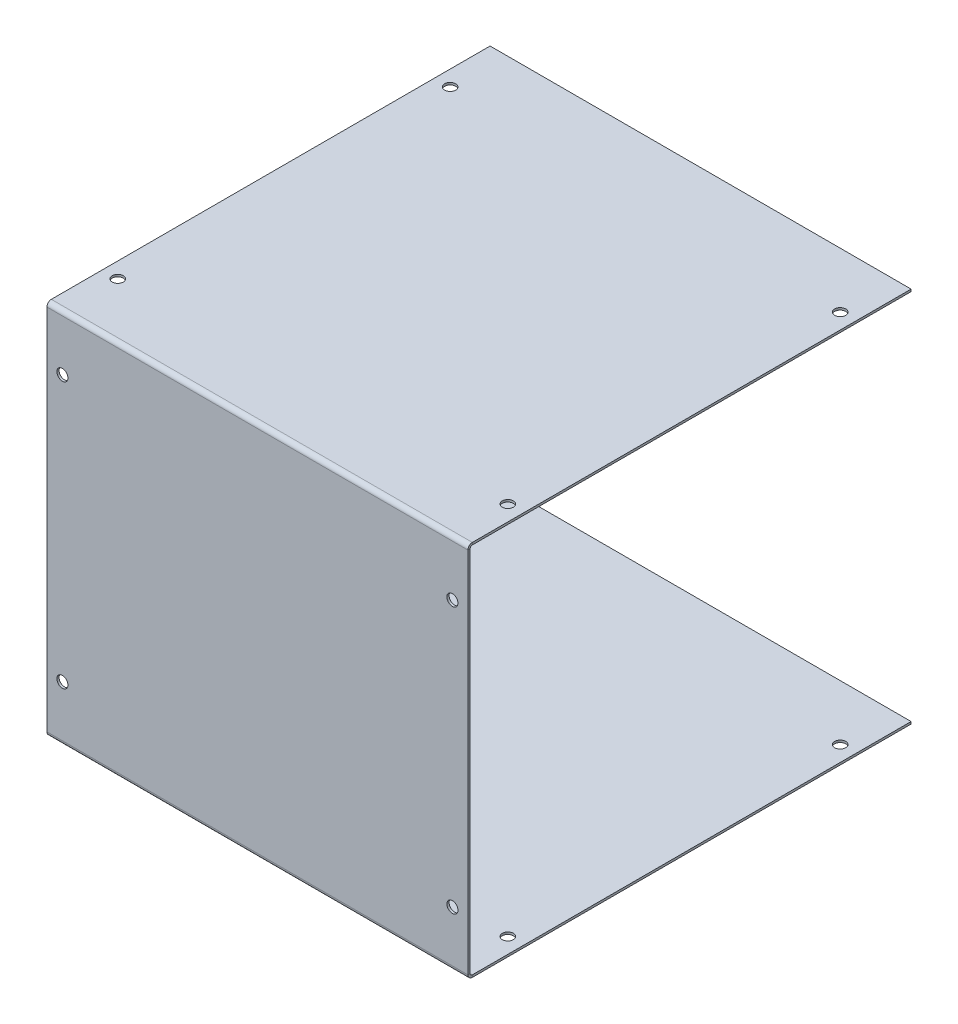
SolidWorks part; units mm, degrees
note: The reader was unsure of these and kept them because the rebuilt part matched: thickness of "Base-Flange1", "Edge-Flange5", "Sheet-Metal1", "Sheet-Metal4", "Sheet-Metal6", "Sheet-Metal7"; flange length of "Edge-Flange5".
material "St.37"
ref_plane "Front Plane" through (0, 0, 0) normal (0, 0, 1) x (1, 0, 0)
ref_plane "Top Plane" through (0, 0, 0) normal (0, 1, 0) x (1, 0, 0)
ref_plane "Right Plane" through (0, 0, 0) normal (1, 0, 0) x (0, 0, -1)
sketch "Sketch1" plane through (0, 0, 0) normal (0, 0, 1) x (1, 0, 0)
  line L1 (-95, -85) -> (95, -85)
  line L2 (-95, -85) -> (-95, 85)
  line L3 (-95, 85) -> (95, 85)
  line L4 (95, -85) -> (95, 85)
  line L5 (-95, -85) -> (95, 85) construction
  line L6 (-95, 85) -> (95, -85) construction
  point P0 (0, 0)
  dimension "D1" = 170
  dimension "D2" = 190
base flange "Base-Flange1" sketch "Sketch1" thickness 1 reverse thickness direction no parameters "D1"=1
sketch "Sketch23" plane through (0, 0, 0) normal (0, 0, 1) x (1, 0, 0)
  line L1 (-95, 85) -> (-95, -85) construction
  line L2 (-95, -85) -> (95, -85) construction
  line L3 (95, -85) -> (95, 85) construction
  circle A4 centre (-88, 60) radius 2.5
  circle A5 centre (88, 60) radius 2.5
  circle A6 centre (88, -60) radius 2.5
  circle A7 centre (-88, -60) radius 2.5
  dimension "D9" = 5
  dimension "D3" = 120
  dimension "D2" = 25
  dimension "D11" = 7
  dimension "D14" = 7
  dimension "D15" = 7
  dimension "D12" = 2
  dimension "D13" = 2
extrude "Cut-Extrude1" cut sketch "Sketch23" against normal blind 10 normal cut yes
edge flange "Edge-Flange5" sketch "Sketch42" flange profiles "Sketch42", "Sketch43" flange angle 90 flange length 200 flange position material inside bend radius 1 thickness 1 relief rectangular parameters "D6"=10, "D8"=1
sketch "Sketch42" plane through (0, 85, -1) normal (0, 1, 0) x (1, 0, 0)
  line L2 (-95, 0) -> (-95, 199)
  line L3 (-95, 199) -> (95, 199)
  line L4 (95, 199) -> (95, 0)
  line L7 (95, 0) -> (-95, 0) construction
  line L8 (95, 0) -> (-95, 0)
sketch "Sketch43" plane through (0, -85, -1) normal (0, -1, 0) x (-1, 0, 0)
  line L0 (95, 0) -> (-95, 0) construction
  line L1 (95, 0) -> (-95, 0)
  line L2 (-95, 0) -> (-95, 199)
  line L3 (-95, 199) -> (95, 199)
  line L4 (95, 199) -> (95, 0)
bend "EdgeBend2" bend radius 1 bend angle 90 parameters "D5"=1
bend "EdgeBend3" bend radius 1 bend angle 90 parameters "D5"=2
sketch "Sketch44" plane through (0, 85, 0) normal (0, 1, 0) x (1, 0, 0)
  line L0 (-95, 200) -> (-95, 2) construction
  line L1 (95, 200) -> (-95, 200) construction
  line L2 (95, 2) -> (95, 200) construction
  circle A0 centre (-88, 175) radius 2.5
  circle A1 centre (88, 175) radius 2.5
  circle A2 centre (88, 25) radius 2.5
  circle A3 centre (-88, 25) radius 2.5
  dimension "D1" = 5
  dimension "D6" = 150
  dimension "D7" = 7
  dimension "D8" = 7
  dimension "D2" = 7
  dimension "D3" = 25
  dimension "D5" = 2
  dimension "D4" = 2
extrude "Cut-Extrude2" cut sketch "Sketch44" against normal blind 180 normal cut yes
sketch "Bend-Lines1" [suppressed] plane through (0, 0, 0) normal (0, 1, 0) x (1, 0, 0)
sketch "Bounding-Box1" [suppressed] plane through (0, 0, 0) normal (0, 1, 0) x (1, 0, 0)
sheet metal parameters "Sheet-Metal1" thickness 1 parameters "D1"=1
flat pattern "Flat-Pattern1" [suppressed]
sketch "Bend-Lines2" plane through (0, 0, 0) normal (0, 1, 0) x (1, 0, 0)
sketch3d "Bounding-Box2" [suppressed]
  line L0 (-100, -85, 0) -> (100, -85, 0) construction
  line L1 (-100, 85, 0) -> (100, 85, 0) construction
  line L2 (-100, -85, 0) -> (-100, 85, 0) construction
  line L3 (100, -85, 0) -> (100, 85, 0) construction
sheet metal parameters "Sheet-Metal4" thickness 1 parameters "D1"=1
flat pattern "Flat-Pattern1"
sketch "Bend-Lines2" plane through (0, 0, 0) normal (0, 1, 0) x (1, 0, 0)
sketch3d "Bounding-Box2" [suppressed]
  line L0 (-100, -85, 0) -> (100, -85, 0) construction
  line L1 (-100, 85, 0) -> (100, 85, 0) construction
  line L2 (-100, -85, 0) -> (-100, 85, 0) construction
  line L3 (100, -85, 0) -> (100, 85, 0) construction
sheet metal parameters "Sheet-Metal6" thickness 1 parameters "D1"=1
flat pattern "Flat-Pattern1"
sketch "Bend-Lines2" plane through (0, 0, 0) normal (0, 0, 1) x (1, 0, 0)
  line L0 (-100, -85.1781) -> (100, -85.1781) construction
  line L1 (100, 85.1781) -> (-100, 85.1781) construction
  line L2 (-100, -85.1781) -> (100, -85.1781) construction
  line L3 (100, 85.1781) -> (-100, 85.1781) construction
sketch3d "Bounding-Box2" [suppressed]
  line L0 (100, 284.3562, 0) -> (100, -284.3562, 0) construction
  line L1 (-100, 284.3562, 0) -> (-100, -284.3562, 0) construction
  line L2 (100, 284.3562, 0) -> (-100, 284.3562, 0) construction
  line L3 (100, -284.3562, 0) -> (-100, -284.3562, 0) construction
bend of the flat pattern "Flatten-<EdgeBend2>1"
bend of the flat pattern "Flatten-<EdgeBend3>1"
sheet metal parameters "Sheet-Metal7" thickness 1 parameters "D1"=1
flat pattern "Flat-Pattern1"
sketch "Bend-Lines2" plane through (0, 0, 0) normal (0, 0, 1) x (1, 0, 0)
  line L0 (-95, -84.1781) -> (95, -84.1781) construction
  line L1 (95, 84.1781) -> (-95, 84.1781) construction
  line L2 (-95, -84.1781) -> (95, -84.1781) construction
  line L3 (95, 84.1781) -> (-95, 84.1781) construction
sketch3d "Bounding-Box2" [suppressed]
  line L0 (95, 283.3562, 0) -> (95, -283.3562, 0) construction
  line L1 (-95, 283.3562, 0) -> (-95, -283.3562, 0) construction
  line L2 (95, 283.3562, 0) -> (-95, 283.3562, 0) construction
  line L3 (95, -283.3562, 0) -> (-95, -283.3562, 0) construction
bend of the flat pattern "Flatten-<EdgeBend2>1"
bend of the flat pattern "Flatten-<EdgeBend3>1"
